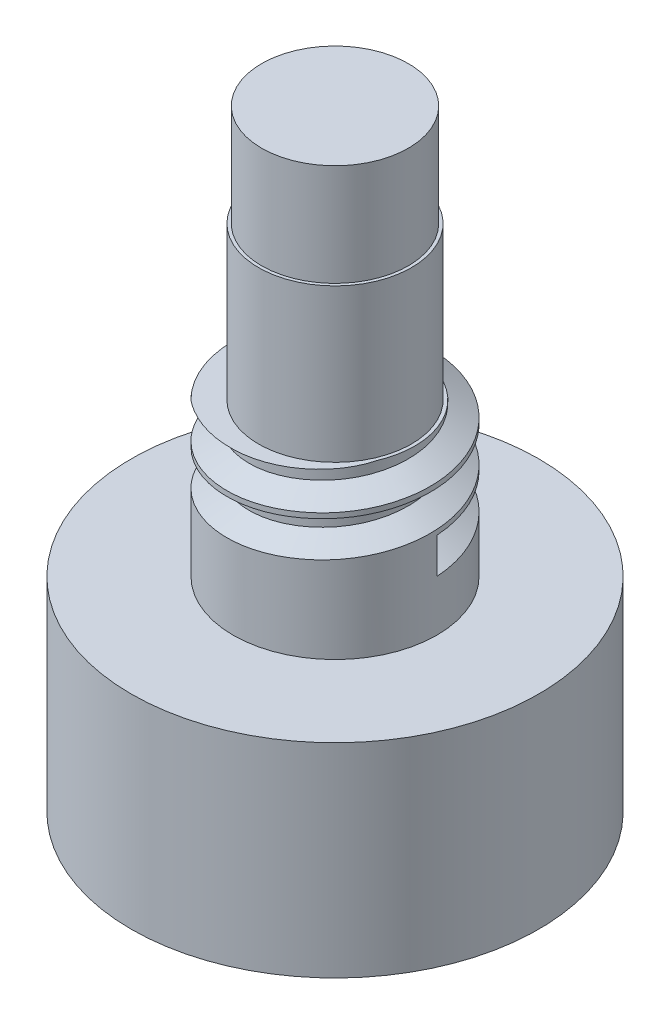
SolidWorks part; units mm, degrees
ref_plane "Front Plane" through (0, 0, 0) normal (0, 0, 1) x (1, 0, 0)
ref_plane "Top Plane" through (0, 0, 0) normal (0, 1, 0) x (1, 0, 0)
ref_plane "Right Plane" through (0, 0, 0) normal (1, 0, 0) x (0, 0, -1)
sketch "Sketch1" plane through (0, 0, 0) normal (0, 1, 0) x (1, 0, 0)
  circle A0 centre (0, 0) radius 2.286
  dimension "D1" = 4.572
extrude "Boss-Extrude1" add sketch "Sketch1" along normal blind 3.175
sketch "Sketch2" plane through (0, 0, 0) normal (0, -1, 0) x (-1, 0, 0)
  circle A0 centre (0, 0) radius 2.3825
  dimension "D1" = 4.765
extrude "Boss-Extrude2" add sketch "Sketch2" along normal blind 4.7622
sketch "Sketch3" plane through (0, -4.7622, 0) normal (0, -1, 0) x (-1, 0, 0)
  circle A0 centre (0, 0) radius 3.175
  dimension "D1" = 6.35
extrude "Boss-Extrude3" add sketch "Sketch3" along normal blind 3.175
sketch "Sketch4" plane through (0, -7.9372, 0) normal (0, -1, 0) x (-1, 0, 0)
  circle A0 centre (0, 0) radius 3.175
  dimension "D1" = 6.35
extrude "Boss-Extrude4" add sketch "Sketch4" along normal blind 1.5875
thread "Thread2" pitch 1.27 method cut profile "Thread Profile3" start angle 0, offset 1.5875, length 3.175, pitch 1.27, diameter 6.35
ref_plane "Plane3" through (3.175, -7.9372, 0) normal (0, 0, 1) x (1, 0, 0)
sketch "Thread Profile3" plane through (3.175, -7.9372, 0) normal (0, 0, 1) x (1, 0, 0)
  line L0 (0, 0) -> (0, 1.27) construction
  line L11 (0, 0) -> (0, 1.1112)
  line L12 (0, 1.1112) -> (-0.6874, 0.7144)
  line L13 (-0.6874, 0.7144) -> (-0.6874, 0.3969)
  line L15 (-0.6874, 0.3969) -> (0, 0)
  line L17 (-0.6874, 0.5556) -> (0, 0.5556) construction
  point P2 (0, 0)
  dimension "Pitch" = 1.27
  dimension "Profile_Angle" = 60
  dimension "Profile_Land" = 0.3175
  dimension "Profile_Height" = 0.6874
sketch "Sketch11" plane through (0, -9.5247, 0) normal (0, -1, 0) x (-1, 0, 0)
  circle A0 centre (0, 0) radius 6.35
  dimension "D1" = 12.7
extrude "Boss-Extrude5" add sketch "Sketch11" along normal blind 6.35
